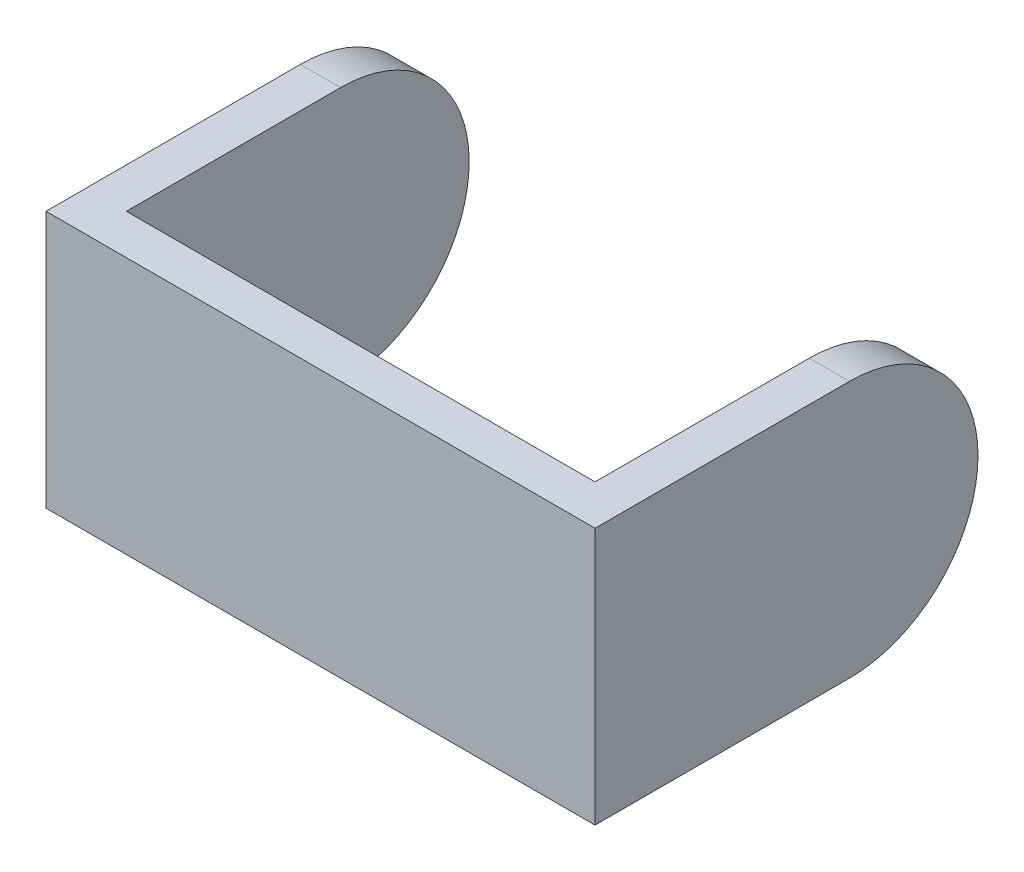
SolidWorks part; units mm, degrees
ref_plane "Front Plane" through (0, 0, 0) normal (0, 0, 1) x (1, 0, 0)
ref_plane "Top Plane" through (0, 0, 0) normal (0, 1, 0) x (1, 0, 0)
ref_plane "Right Plane" through (0, 0, 0) normal (1, 0, 0) x (0, 0, -1)
sketch "Sketch1" plane through (0, 0, 0) normal (1, 0, 0) x (0, 0, -1)
  line L0 (0, -9.6) -> (-16, -9.6)
  line L1 (0, 9.6) -> (-16, 9.6)
  line L3 (-16, -9.6) -> (-19, -9.6)
  line L4 (-16, -9.6) -> (-16, 9.6)
  line L5 (-16, 9.6) -> (-19, 9.6)
  line L6 (-19, -9.6) -> (-19, 9.6)
  circle A0 centre (0, 0) radius 9.6
  dimension "D1" = 19.2
  dimension "D2" = 16
  dimension "D3" = 3
extrude "Boss-Extrude1" add sketch "Sketch1" along normal blind 3 contours A0 | A0 L1 L4 L0 | L6 L3 L4 L5 region at (0, 0, 11.4986) region at (0, 0, 0) region at (0, 0, 17.5)
extrude "Boss-Extrude2" add sketch "Sketch1<3>" against normal blind 38 contours L6 L3 L4 L5 region at (0, 0, 17.5)
sketch "Sketch1<3>" plane through (0, 0, 0) normal (1, 0, 0) x (0, 0, -1) same geometry as "Sketch1"
extrude "Boss-Extrude3" add sketch "Sketch1<4>" against normal blind 38 contours A0 L1 L4 L0 | A0 region at (0, 0, 11.4986) region at (0, 0, 0)
sketch "Sketch1<4>" plane through (0, 0, 0) normal (1, 0, 0) x (0, 0, -1) same geometry as "Sketch1"
extrude "Cut-Extrude1" cut sketch "Sketch1<5>" against normal blind 35 contours A0 | A0 L1 L4 L0 region at (0, 0, 11.4986) region at (0, 0, 0)
sketch "Sketch1<5>" plane through (0, 0, 0) normal (1, 0, 0) x (0, 0, -1) same geometry as "Sketch1"
